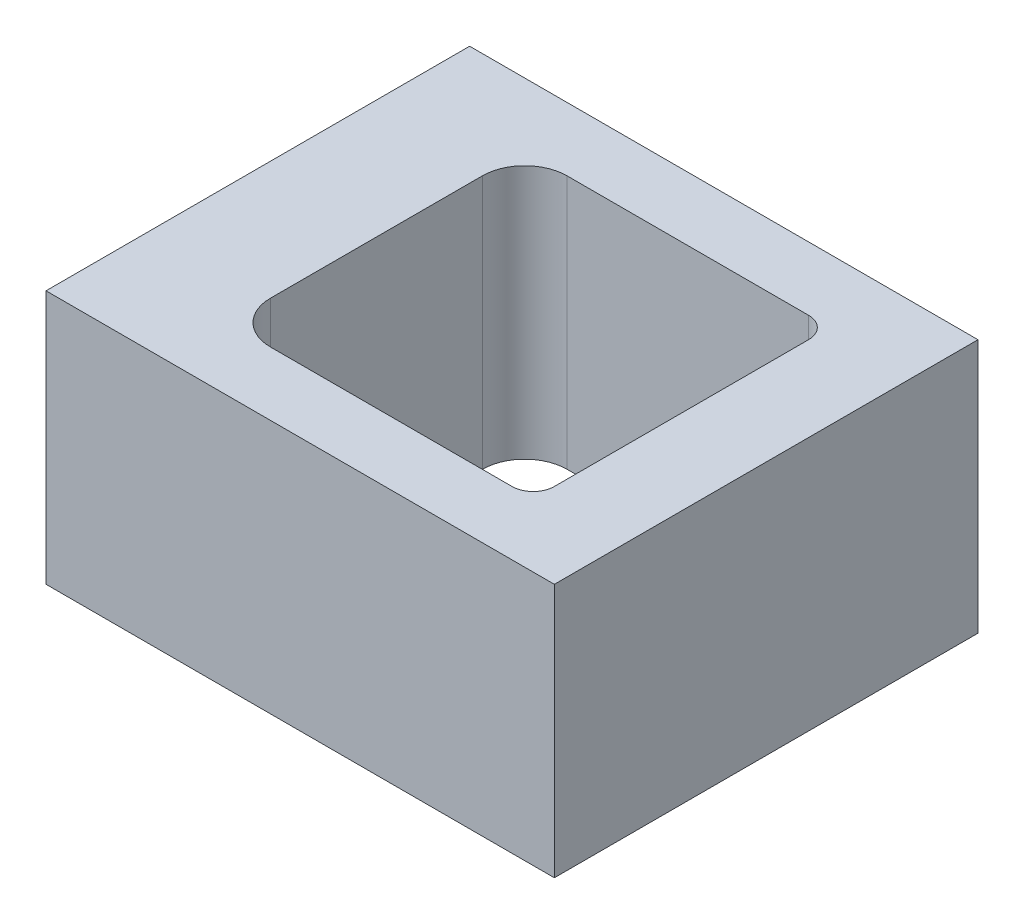
SolidWorks part; units mm, degrees
ref_plane "Front Plane" through (0, 0, 0) normal (0, 0, 1) x (1, 0, 0)
ref_plane "Top Plane" through (0, 0, 0) normal (0, 1, 0) x (1, 0, 0)
ref_plane "Right Plane" through (0, 0, 0) normal (1, 0, 0) x (0, 0, -1)
sketch "Sketch1" plane through (0, 0, 0) normal (0, 1, 0) x (1, 0, 0)
  line L0 (-40.64, 31.75) -> (-40.64, -31.75) construction
  line L1 (-76.2, -63.5) -> (76.2, -63.5)
  line L2 (-76.2, -63.5) -> (-76.2, 63.5)
  line L3 (-76.2, 63.5) -> (76.2, 63.5)
  line L4 (76.2, -63.5) -> (76.2, 63.5)
  line L5 (-76.2, -63.5) -> (76.2, 63.5) construction
  line L6 (-76.2, 63.5) -> (76.2, -63.5) construction
  line L7 (44.45, 44.45) -> (-27.94, 44.45) construction
  line L8 (50.8, 38.1) -> (50.8, -38.1) construction
  line L9 (44.45, -44.45) -> (-27.94, -44.45) construction
  line L10 (-40.64, 31.75) -> (-40.64, -31.75)
  line L11 (44.45, 44.45) -> (-27.94, 44.45)
  line L12 (50.8, 38.1) -> (50.8, -38.1)
  line L13 (44.45, -44.45) -> (-27.94, -44.45)
  arc A0 (-27.94, 44.45) -> (-40.64, 31.75) centre (-27.94, 31.75) ccw construction
  arc A1 (50.8, 38.1) -> (44.45, 44.45) centre (44.45, 38.1) ccw construction
  arc A2 (44.45, -44.45) -> (50.8, -38.1) centre (44.45, -38.1) ccw construction
  arc A3 (-40.64, -31.75) -> (-27.94, -44.45) centre (-27.94, -31.75) ccw construction
  arc A4 (-27.94, 44.45) -> (-40.64, 31.75) centre (-27.94, 31.75) ccw
  arc A5 (50.8, 38.1) -> (44.45, 44.45) centre (44.45, 38.1) ccw
  arc A6 (44.45, -44.45) -> (50.8, -38.1) centre (44.45, -38.1) ccw
  arc A7 (-40.64, -31.75) -> (-27.94, -44.45) centre (-27.94, -31.75) ccw
  point P0 (0, 0)
  dimension "D1" = 127
  dimension "D2" = 152.4
extrude "Boss-Extrude1" add sketch "Sketch1" along normal blind 76.2
